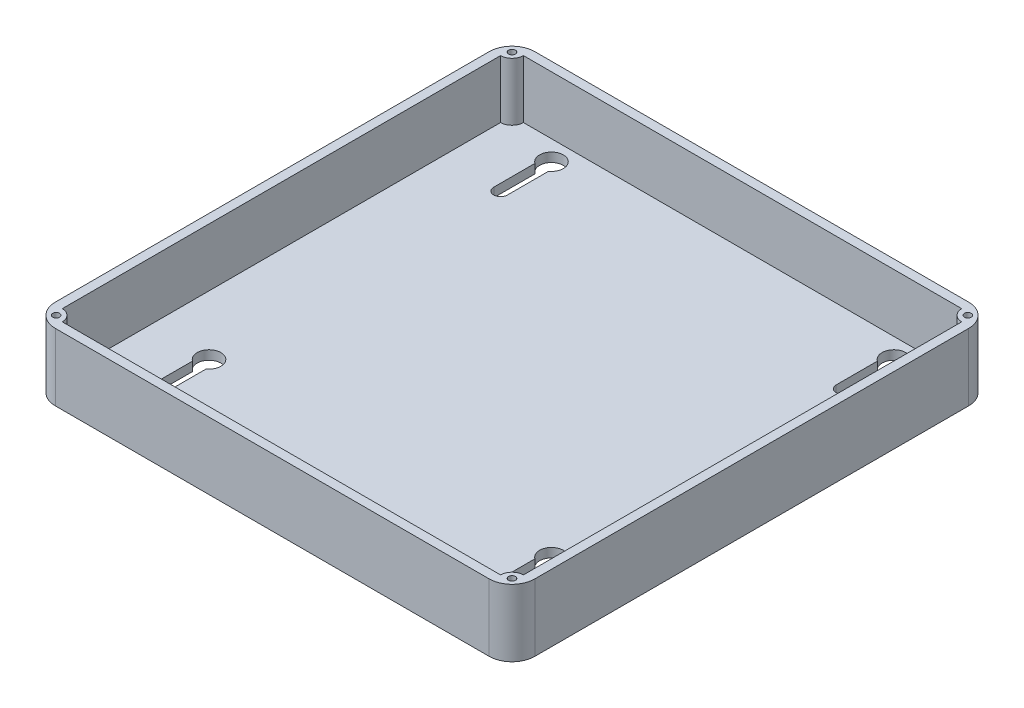
SolidWorks part; units mm, degrees
ref_plane "Front Plane" through (0, 0, 0) normal (0, 0, 1) x (1, 0, 0)
ref_plane "Top Plane" through (0, 0, 0) normal (0, 1, 0) x (1, 0, 0)
ref_plane "Right Plane" through (0, 0, 0) normal (1, 0, 0) x (0, 0, -1)
sketch "Sketch1" plane through (0, 0, 0) normal (0, 1, 0) x (1, 0, 0)
  line L0 (-101, -101) -> (-101, 101)
  line L1 (-105, -105) -> (105, -105)
  line L2 (-105, -105) -> (-105, 105)
  line L3 (-105, 105) -> (105, 105)
  line L4 (105, -105) -> (105, 105)
  line L5 (-101, 101) -> (101, 101)
  line L6 (101, -101) -> (101, 101)
  line L7 (-101, -101) -> (101, -101)
  point P0 (0, 0)
  point P6 (0, 105)
  point P7 (-105, 0)
  dimension "D1" = 210
  dimension "D2" = 210
  dimension "D3" = 4
extrude "Base" add sketch "Sketch1" along normal blind 4 contours L1 L4 L3 L2
extrude "Walls" add sketch "Sketch1<3>" along normal blind 25.4 from surface starting at face at (0, 4, 0)
sketch "Sketch1<3>" plane through (0, 0, 0) normal (0, 1, 0) x (1, 0, 0) same geometry as "Sketch1"
sketch "Sketch2" plane through (0, 29.4, 0) normal (0, 1, 0) x (1, 0, 0)
  line L0 (-101, 101) -> (-101, 96)
  line L1 (-101, 101) -> (-101, -101) construction
  line L2 (-101, 101) -> (-96, 101)
  line L3 (101, 101) -> (-101, 101) construction
  line L12 (-101, 101) -> (-97.4645, 97.4645) construction
  line L27 (-16.72, 0) -> (16.72, 0) construction
  line L28 (-101, -101) -> (-101, -96)
  line L29 (-101, -101) -> (-96, -101)
  line L30 (0, -16.72) -> (0, 16.72) construction
  line L31 (101, 101) -> (101, 96)
  line L32 (101, 101) -> (96, 101)
  line L33 (101, -101) -> (96, -101)
  line L34 (101, -101) -> (101, -96)
  arc A0 (-101, 96) -> (-96, 101) centre (-101, 101) ccw
  circle A18 centre (-99.8333, 99.8333) radius 1.5
  arc A19 (-101, -96) -> (-96, -101) centre (-101, -101) cw
  circle A20 centre (-99.8333, -99.8333) radius 1.5
  arc A21 (101, 96) -> (96, 101) centre (101, 101) cw
  circle A22 centre (99.8333, 99.8333) radius 1.5
  circle A23 centre (99.8333, -99.8333) radius 1.5
  arc A24 (101, -96) -> (96, -101) centre (101, -101) ccw
  dimension "D2" = 1.65
  dimension "D3" = 3
  dimension "D1" = 5
extrude "ScrewMounts" add sketch "Sketch2" against normal up to surface (25.4 mm away) contours A0 L2 L0 | A20 | L28 A19 L29 | L33 A24 L34 | L31 A21 L32 up to face at (0, 4, 0)
extrude "ScrewHoles" cut sketch "Sketch2<5>" against normal blind 12.5 contours A23 | A18 | A20 | A22
sketch "Sketch2<5>" plane through (0, 29.4, 0) normal (0, 1, 0) x (1, 0, 0) same geometry as "Sketch2"
fillet "RoundedCorners" radius 10 4 edges at (-105, 14.7, -105) (105, 14.7, -105) (105, 14.7, 105) (-105, 14.7, 105)
sketch "Sketch3" plane through (0, 0, 0) normal (0, -1, 0) x (1, 0, 0)
  line L0 (-77.985, 80) -> (-77.985, 61.974)
  line L1 (-72.015, 80) -> (-72.015, 61.974)
  line L2 (-105, 95) -> (-105, -95) construction
  line L3 (-95, 105) -> (95, 105) construction
  line L4 (0, -16.72) -> (0, 16.72) construction
  line L5 (77.985, 80) -> (77.985, 61.974)
  line L6 (72.015, 80) -> (72.015, 61.974)
  line L7 (-75, 57.71) -> (75, 57.71) construction
  line L8 (-75, 57.71) -> (-75, -92.29) construction
  line L9 (72.015, -70) -> (72.015, -88.026)
  line L10 (-77.985, -70) -> (-77.985, -88.026)
  line L11 (-72.015, -70) -> (-72.015, -88.026)
  line L12 (77.985, -70) -> (77.985, -88.026)
  arc A0 (-77.985, 61.974) -> (-72.015, 61.974) centre (-75, 57.71) ccw
  arc A1 (-72.015, 80) -> (-77.985, 80) centre (-75, 80) ccw
  arc A2 (72.015, 80) -> (77.985, 80) centre (75, 80) cw
  arc A3 (77.985, 61.974) -> (72.015, 61.974) centre (75, 57.71) cw
  arc A6 (-77.985, -88.026) -> (-72.015, -88.026) centre (-75, -92.29) ccw
  arc A7 (-77.985, -70) -> (-72.015, -70) centre (-75, -70) cw
  arc A8 (77.985, -70) -> (72.015, -70) centre (75, -70) ccw
  arc A9 (77.985, -88.026) -> (72.015, -88.026) centre (75, -92.29) cw
  point P36 (0, 0)
  dimension "D2" = 10.41
  dimension "D3" = 5.97
  dimension "D7" = 150
  dimension "D1" = 22.29
  dimension "D4" = 30
  dimension "D5" = 25
  dimension "D6" = 150
extrude "BackHoleMounts" cut sketch "Sketch3" against normal up to surface (4 mm away) up to face at (0, 4, 0)
